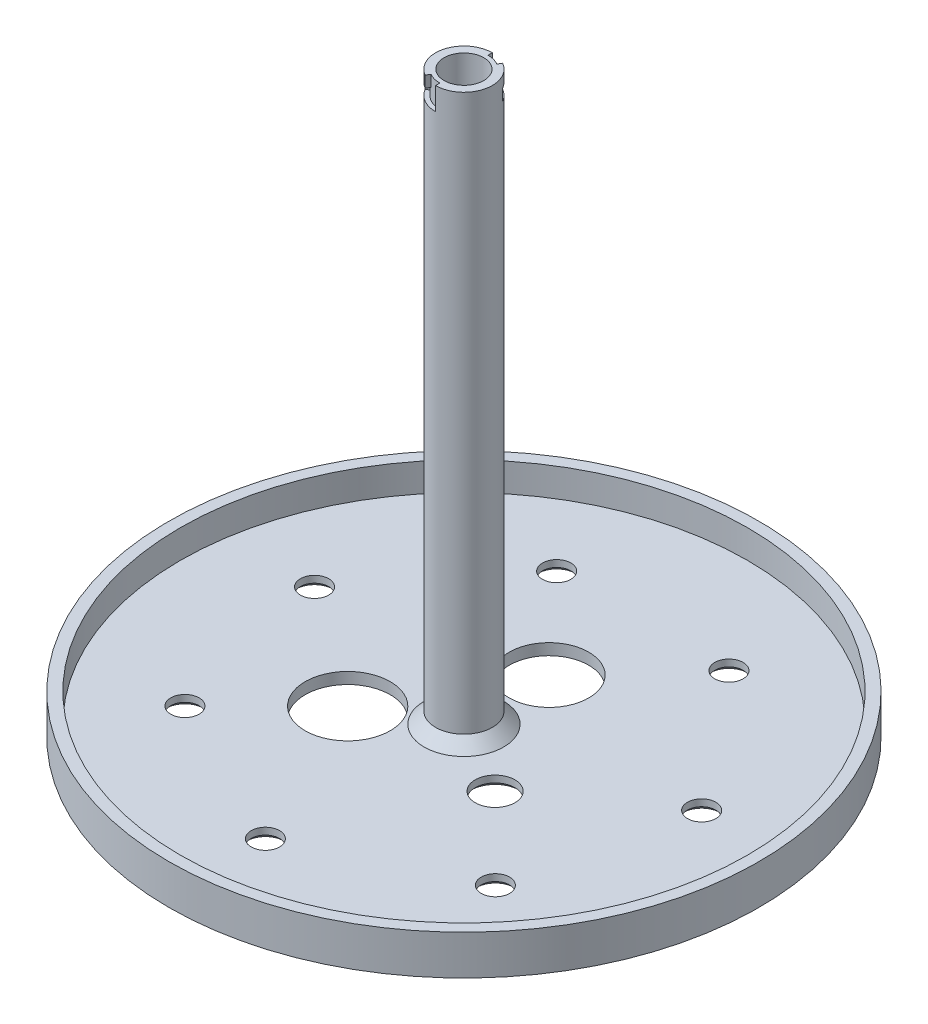
SolidWorks part; units mm, degrees
ref_plane "Front Plane" through (0, 0, 0) normal (0, 0, 1) x (1, 0, 0)
ref_plane "Top Plane" through (0, 0, 0) normal (0, 1, 0) x (1, 0, 0)
ref_plane "Right Plane" through (0, 0, 0) normal (1, 0, 0) x (0, 0, -1)
sketch "Sketch1" plane through (0, 0, 0) normal (0, 1, 0) x (1, 0, 0)
  line L0 (0, 15) -> (0, 0) construction
  line L1 (0, 0) -> (-12.9904, -7.5) construction
  line L2 (0, 0) -> (12.9904, -7.5) construction
  circle A0 centre (0, 0) radius 50
  circle A1 centre (0, 15) radius 7
  circle A2 centre (-12.9904, -7.5) radius 7.5
  circle A3 centre (12.9904, -7.5) radius 3.5
  circle A4 centre (0, 0) radius 3.5
  point P3 (0, 15)
  point P8 (12.9904, -7.5)
  point P9 (-12.9904, -7.5)
  point P10 (0, 0)
  dimension "D1" = 100
  dimension "D4" = 14
  dimension "D5" = 15
  dimension "D6" = 7
  dimension "D7" = 7
  dimension "D2" = 15
  dimension "D3" = 3
extrude "Boss-Extrude1" add sketch "Sketch1" along normal blind 2
sketch "Sketch2" plane through (0, 2, 0) normal (0, 1, 0) x (1, 0, 0)
  line L0 (0, 0) -> (12.9904, -7.5) construction
  line L1 (0, 0) -> (0, 50) construction
  line L2 (0, 0) -> (-12.9904, -7.5) construction
  line L3 (0, 0) -> (-43.3013, -25) construction
  line L4 (0, 0) -> (43.3013, -25) construction
  circle A0 centre (0, 0) radius 50 construction
  circle A1 centre (-12.9904, -7.5) radius 7.5 construction
  circle A2 centre (12.9904, -7.5) radius 3.5 construction
  circle A3 centre (0, 0) radius 25
  circle A4 centre (21.6506, -12.5) radius 3
  circle A5 centre (-21.6506, -12.5) radius 3
  circle A6 centre (0, 25) radius 3
  point P22 (0, 0)
  dimension "D1" = 50
  dimension "D2" = 6
  dimension "D3" = 3
ref_plane "Plane1" through (0, 0, 0) normal (-0.5, 0, -0.866) x (-0.866, 0, 0.5)
sketch "Sketch3" plane through (0, 2, 0) normal (0, 1, 0) x (1, 0, 0)
  circle A0 centre (0, 0) radius 3.5
  circle A1 centre (0, 0) radius 5
  dimension "D1" = 10
extrude "Boss-Extrude2" add sketch "Sketch3" along normal blind 100
sketch "Sketch6" plane through (0, 0, 0) normal (0, -1, 0) x (1, 0, 0)
  circle A0 centre (0, 0) radius 35
  circle A1 centre (0, 35) radius 2.5
  circle A2 centre (27.3641, 21.8221) radius 2.5
  circle A3 centre (34.1225, -7.7882) radius 2.5
  circle A4 centre (15.1859, -31.5339) radius 2.5
  circle A5 centre (-15.1859, -31.5339) radius 2.5
  circle A6 centre (-34.1225, -7.7882) radius 2.5
  circle A7 centre (-27.3641, 21.8221) radius 2.5
  point P20 (0, 0)
  dimension "D1" = 70
  dimension "D2" = 5
  dimension "D3" = 7
extrude "Cut-Extrude2" cut sketch "Sketch6" against normal up to next contours A0 A4 | A0 A4 | A0 A3 | A0 A3 | A0 A2 | A0 A2 | A0 A1 | A0 A1 | A0 A7 | A0 A7 | A0 A6 | A0 A6 | A0 A5 | A0 A5 region at (26.5221, 0, 21.1507) region at (28.181, 0, 22.4736) region at (35.1411, 0, -8.0207) region at (33.0725, 0, -7.5486) region at (0, 0, 33.923) region at (0, 0, 36.0448) region at (15.6392, 0, -32.4752) region at (14.7187, 0, -30.5636) region at (-26.5221, 0, 21.1507) region at (-28.181, 0, 22.4736) region at (-15.6392, 0, -32.4752) region at (-14.7187, 0, -30.5636) region at (-33.0725, 0, -7.5486) region at (-35.1411, 0, -8.0207)
chamfer "Chamfer2" distance 0.8 angle 45 8 edges at (0, 0, 32.5) (-27.3641, 0, 19.3221) (-34.1225, 0, -10.2882) (-15.1859, 0, -34.0339) (27.3641, 0, 19.3221) (12.9904, 0, 11) (34.1225, 0, -10.2882) (15.1859, 0, -34.0339)
ref_axis "Axis1" through (0, 102, 0) along (0, -1, 0)
sketch "Sketch7" plane through (0, 0, 0) normal (1, 0, 0) x (0, 0, -1)
  line L1 (5, 102) -> (4.25, 102)
  line L2 (5, 102) -> (5, 100)
  line L3 (5, 100) -> (4.25, 100)
  line L4 (4.25, 102) -> (4.25, 100)
  line L5 (5, 100) -> (4.25, 100)
  line L6 (5, 100) -> (5, 98)
  line L7 (5, 98) -> (4.25, 98)
  line L8 (4.25, 100) -> (4.25, 98)
  dimension "D1" = 2
  dimension "D2" = 0.75
  dimension "D3" = 2
  dimension "D4" = 0.75
revolve "Cut-Revolve1" cut sketch "Sketch7" angle 30 about axis through (0, 102, 0) along (0, -1, 0) region at (0, 101, -4.625)
revolve "Cut-Revolve2" cut sketch "Sketch7<4>" angle 60 about axis through (0, 102, 0) along (0, -1, 0) region at (0, 99, -4.625)
sketch "Sketch7<4>" plane through (0, 0, 0) normal (1, 0, 0) x (0, 0, -1) same geometry as "Sketch7"
pattern_circular "CirPattern5" count 2 over 360 about axis through (0, 102, 0) along (0, -1, 0) of "Cut-Revolve2", "Cut-Revolve1"
sketch "Sketch8" plane through (0, 2, 0) normal (0, 1, 0) x (1, 0, 0)
  circle A0 centre (0, 0) radius 50
  circle A1 centre (0, 0) radius 52
  dimension "D1" = 100
  dimension "D2" = 104
extrude "Boss-Extrude3" add sketch "Sketch8" along normal blind 5 and the other way blind 2 separate body
chamfer "Chamfer3" distance 2 angle 45 1 edges at (0, 2, 5)
